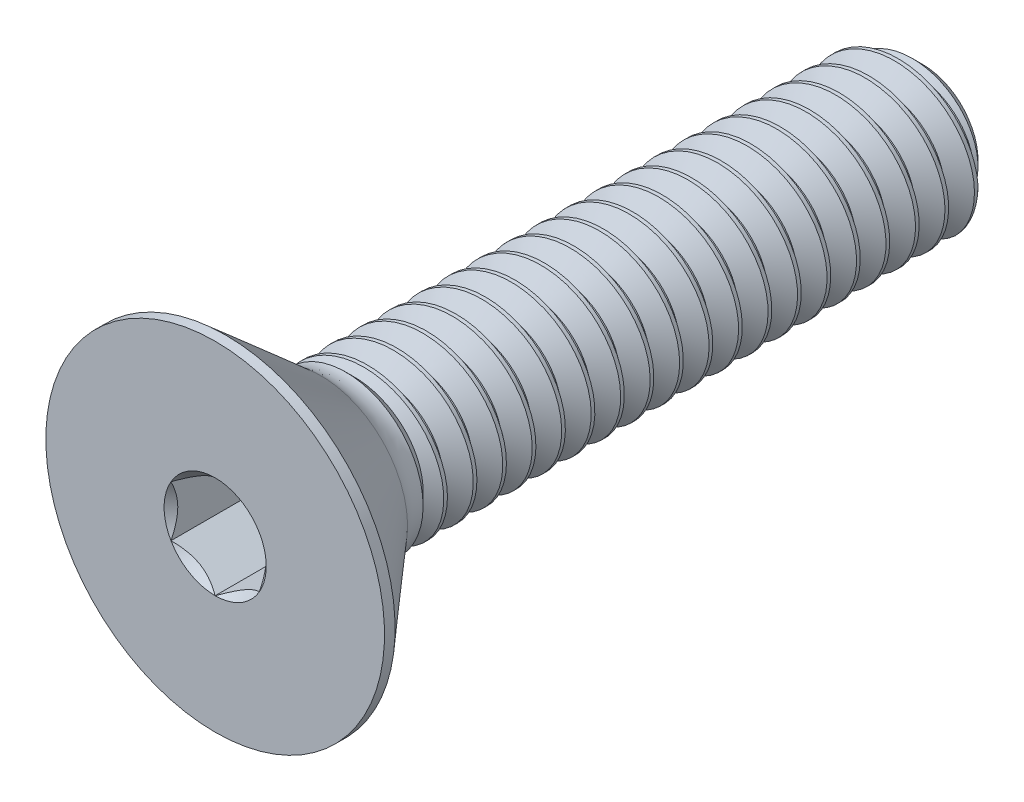
SolidWorks part; units mm, degrees
ref_plane "Front" through (0, 0, 0) normal (0, 0, 1) x (1, 0, 0)
ref_plane "Top" through (0, 0, 0) normal (0, 1, 0) x (1, 0, 0)
ref_plane "Right" through (0, 0, 0) normal (1, 0, 0) x (0, 0, -1)
sketch "Sketch1" plane through (0, 0, 0) normal (1, 0, 0) x (0, 0, -1)
  line L0 (0, 4.5593) -> (0.2845, 4.5593) construction
  line L1 (0.2845, 4.5593) -> (2.8448, 2.3336) construction
  line L2 (0, 2.0828) -> (19.05, 2.0828)
  line L3 (19.05, 2.0828) -> (19.05, 0)
  line L4 (19.05, 0) -> (0, 0)
  line L5 (0, 0) -> (0, 4.5593) construction
  line L6 (0, 4.5593) -> (0, -4.5593) construction
  line L7 (19.05, 2.0828) -> (19.05, -2.0828) construction
  line L8 (0, -4.5593) -> (0.2845, -4.5593) construction
  line L9 (0.2845, -4.5593) -> (2.8448, -2.3336) construction
  line L11 (0, 2.0828) -> (0, 0)
  line L12 (3.5157, 2.0828) -> (3.5157, 0) construction
  arc A1 (2.8448, 2.3336) -> (3.5157, 2.0828) centre (3.5157, 3.1055) ccw construction
  dimension "D1" = 0.2845
  dimension "Head Ht" = 2.8448
  dimension "Head Dia" = 9.1186
  dimension "Dia" = 4.1656
  dimension "Lg" = 19.05
  dimension "Head Angle" = 82
revolve "Revolve1" add sketch "Sketch1" angle 360 mid plane about L4
sketch "Sketch3" plane through (0, 0, -19.05) normal (0, 0, -1) x (-1, 0, 0)
  circle A0 centre (0, 0) radius 2.0828
curve "Helix/Spiral1" pitch 0.7937 height 19.05 turns 24
sketch "Sketch2" plane through (0, 0, 0) normal (1, 0, 0) x (0, 0, -1)
  line L0 (19.05, 2.0828) -> (19.7445, 2.0828)
  line L1 (19.7445, 2.0828) -> (19.4469, 1.5672)
  line L2 (19.4469, 1.5672) -> (19.3477, 1.5672)
  line L3 (19.3477, 1.5672) -> (19.05, 2.0828)
  line L4 (19.1988, 1.825) -> (19.5957, 1.825) construction
  dimension "D1" = 60
  dimension "D2" = 0.0992
  dimension "D3" = 0.3969
chamfer "Chamfer1" distance 0.5953 angle 45 1 edges at (0, 2.0828, -19.05)
sweep "Cut-Sweep1" cut profiles "Sketch2" path "Helix/Spiral1"
sketch "Sketch7" plane through (0, 0, 0) normal (1, 0, 0) x (0, 0, -1)
  line L0 (0, 4.5593) -> (0.2845, 4.5593) construction
  line L1 (0.2845, 4.5593) -> (2.8448, 2.3336) construction
  line L2 (0, 4.5593) -> (0.2845, 4.5593)
  line L3 (0.2845, 4.5593) -> (2.8448, 2.3336)
  line L4 (3.5157, 2.0828) -> (3.5157, 0) construction
  line L5 (3.5157, 2.0828) -> (3.5157, 0)
  line L7 (0, 0) -> (0, 4.5593) construction
  line L8 (0, 0) -> (0, 4.5593)
  line L9 (0, 0) -> (3.5157, 0)
  line L10 (5.0152, 0) -> (-5.0152, 0) construction
  arc A0 (2.8448, 2.3336) -> (3.5157, 2.0828) centre (3.5157, 3.1055) ccw construction
  arc A1 (2.8448, 2.3336) -> (3.5157, 2.0828) centre (3.5157, 3.1055) ccw
revolve "Revolve2" add sketch "Sketch7" angle 360 mid plane about L9
ref_plane "Plane1" through (0, 0, -3.5157) normal (0, 0, 1) x (1, 0, 0)
sketch "Sketch8" plane through (0, 0, -3.5157) normal (0, 0, 1) x (1, 0, 0)
  circle A0 centre (0, 0) radius 2.0828
extrude "Boss-Extrude1" add sketch "Sketch8" against normal through all draft 45
sketch "Sketch5" plane through (0, 0, 0) normal (0, 0, 1) x (1, 0, 0)
  line L1 (1.1906, -0.6874) -> (1.1906, 0.6874)
  line L2 (1.1906, 0.6874) -> (0, 1.3748)
  line L3 (0, 1.3748) -> (-1.1906, 0.6874)
  line L4 (-1.1906, 0.6874) -> (-1.1906, -0.6874)
  line L5 (-1.1906, -0.6874) -> (0, -1.3748)
  line L6 (0, -1.3748) -> (1.1906, -0.6874)
  circle A0 centre (0, 0) radius 1.1906 construction
  dimension "Hex" = 2.3813
extrude "Cut-Extrude2" cut sketch "Sketch5" against normal blind 1.9914
sketch "Sketch6" plane through (0, 0, 0) normal (0, 0, 1) x (1, 0, 0)
  circle A0 centre (0, 0) radius 1.3748
extrude "Cut-Extrude3" cut sketch "Sketch6" against normal blind 1.9914 draft 45
sketch "Sketch9" [suppressed] plane through (0, 0, -3.5157) normal (0, 0, 1) x (1, 0, 0)
  circle A1 centre (0, 0) radius 2.0828
  circle A2 centre (0, 0) radius 2.0828
  point P0 (0, 2.0828)
  dimension "D1" = 0
extrude "Boss-Extrude2" [suppressed] add sketch "Sketch9" against normal offset from surface (6.0093 mm away) 22.225
sketch "Sketch10" plane through (0, 0, 0) normal (1, 0, 0) x (0, 0, -1)
  line L0 (19.05, 2.0828) -> (19.05, -2.0828) construction
  point P0 (17.8594, -2.0828)
  dimension "D1" = 1.1906
equation "\"D3@Helix/Spiral1\" = \"Lg@Sketch1\""
equation "\"D2@Sketch2\" = \"D4@Helix/Spiral1\" * .125"
equation "\"D3@Sketch2\" = \"D4@Helix/Spiral1\" * .5"
equation "\"D1@Chamfer1\" = \"D4@Helix/Spiral1\" * .75"
equation "\"D1@Cut-Extrude2\" = \"Head Ht@Sketch1\" * .7"
equation "\"D1@Sketch1\" = \"Head Ht@Sketch1\" * .1"
equation "\"D1@Sketch10\" = \"D4@Helix/Spiral1\" * 1.5"
equation "\"D1@Cut-Extrude3\" = \"D1@Cut-Extrude2\""
